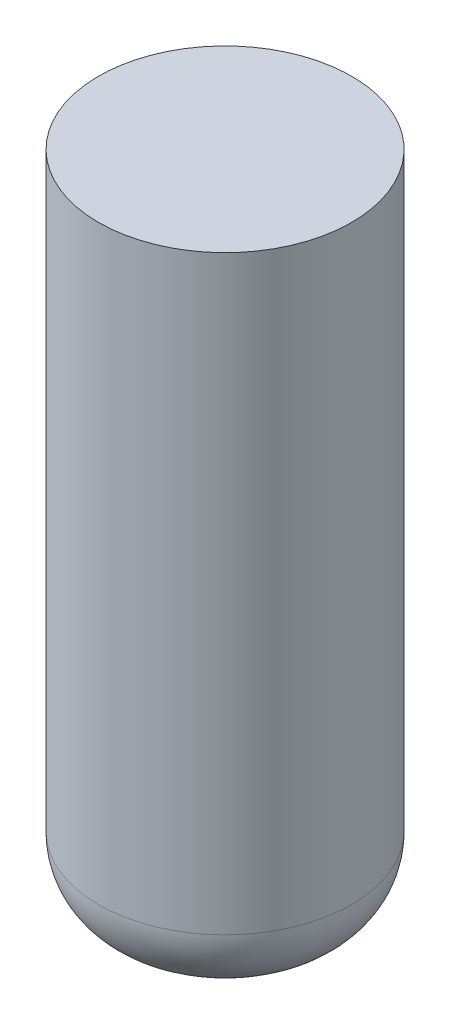
SolidWorks part; units mm, degrees
ref_plane "Front Plane" through (0, 0, 0) normal (0, 0, 1) x (1, 0, 0)
ref_plane "Top Plane" through (0, 0, 0) normal (0, 1, 0) x (1, 0, 0)
ref_plane "Right Plane" through (0, 0, 0) normal (1, 0, 0) x (0, 0, -1)
sketch "Sketch1" plane through (0, 0, 0) normal (0, 1, 0) x (1, 0, 0)
  circle A0 centre (0, 0) radius 2.1
  dimension "D1" = 4.2
extrude "Boss-Extrude1" add sketch "Sketch1" along normal blind 11
fillet "Fillet2" radius 1.2 1 edges at (0, 0, 2.1)
